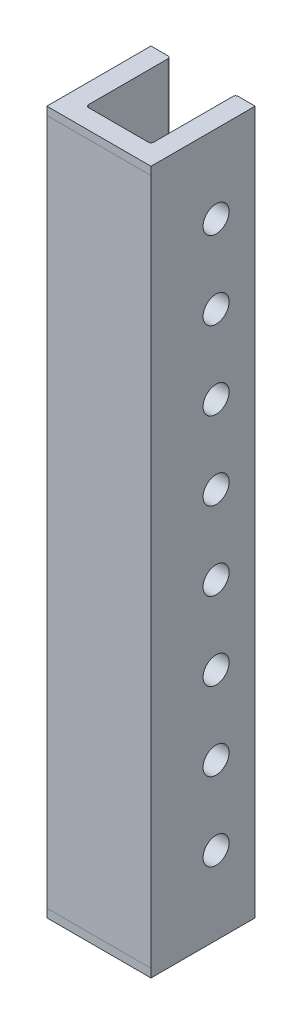
SolidWorks part; units mm, degrees
material "Plain Carbon Steel"
ref_plane "Front Plane" through (0, 0, 0) normal (0, 0, 1) x (1, 0, 0)
ref_plane "Top Plane" through (0, 0, 0) normal (0, 1, 0) x (1, 0, 0)
ref_plane "Right Plane" through (0, 0, 0) normal (1, 0, 0) x (0, 0, -1)
sketch "Sketch1" plane through (0, 0, 0) normal (0, 1, 0) x (1, 0, 0)
  line L0 (0, 0) -> (50.8, 0) construction
  line L1 (0, 0) -> (0, 9.525) construction
  line L2 (50.8, 0) -> (50.8, 9.525) construction
  line L3 (0, 9.525) -> (50.8, 9.525) construction
  line L4 (0, 0) -> (0, 50.8) construction
  line L5 (0, 50.8) -> (9.525, 50.8) construction
  line L6 (9.525, 50.8) -> (9.525, 9.525) construction
  line L7 (9.525, 9.525) -> (41.275, 9.525) construction
  line L8 (41.275, 9.525) -> (41.275, 50.8) construction
  line L9 (41.275, 50.8) -> (50.8, 50.8) construction
  line L10 (50.8, 50.8) -> (50.8, 9.525) construction
  line L11 (0, 0) -> (50.8, 0)
  line L12 (50.8, 0) -> (50.8, 50.8)
  line L13 (50.8, 50.8) -> (41.275, 50.8)
  line L14 (41.275, 50.8) -> (41.275, 9.525)
  line L15 (41.275, 9.525) -> (9.525, 9.525)
  line L16 (9.525, 9.525) -> (9.525, 50.8)
  line L17 (9.525, 50.8) -> (0, 50.8)
  line L18 (0, 50.8) -> (0, 0)
  dimension "D1" = 50.8
  dimension "D2" = 9.525
  dimension "D3" = 50.8
  dimension "D4" = 9.525
  dimension "D5" = 9.525
  dimension "D6" = 9.525
extrude "Boss-Extrude1" add sketch "Sketch1" along normal blind 342.9 contours L15 L16 L17 L18 L11 L12 L13 L14
sketch "Sketch2" plane through (50.8, 0, 0) normal (1, 0, 0) x (0, 0, -1)
  line L0 (31.75, 342.9) -> (31.75, 0) construction
  line L1 (0, 0) -> (50.8, 0) construction
  line L3 (31.75, 171.45) -> (0, 171.45) construction
  line L4 (0, 342.9) -> (0, 0) construction
  line L5 (0, 171.45) -> (50.8, 171.45) construction
  line L6 (50.8, 342.9) -> (50.8, 0) construction
  line L8 (0, 342.9) -> (50.8, 342.9) construction
  circle A0 centre (31.75, 304.8) radius 6.35
  circle A1 centre (31.75, 190.5) radius 6.35
  circle A2 centre (31.75, 228.6) radius 6.35
  circle A3 centre (31.75, 266.7) radius 6.35
  circle A4 centre (31.75, 76.2) radius 6.35
  circle A5 centre (31.75, 38.1) radius 6.35
  circle A7 centre (31.75, 152.4) radius 6.35
  circle A8 centre (31.75, 114.3) radius 6.35
  dimension "D1" = 38.1
  dimension "D2" = 171.45
  dimension "D5" = 12.7
  dimension "D6" = 12.7
  dimension "D7" = 12.7
  dimension "D8" = 152.4
  dimension "D11" = 12.7
  dimension "D12" = 12.7
  dimension "D13" = 12.7
  dimension "D15" = 12.7
  dimension "D16" = 12.7
  dimension "D3" = 76.2
  dimension "D4" = 114.3
  dimension "D9" = 19.05
  dimension "D10" = 190.5
  dimension "D14" = 228.6
  dimension "D17" = 38.1
  dimension "D18" = 38.1
  dimension "D19" = 38.1
extrude "Cut-Extrude1" cut sketch "Sketch2" against normal blind 304.8
fillet "Fillet1" radius 1.27 4 edges at (41.275, 171.45, -9.525) (9.525, 171.45, -50.8) (41.275, 171.45, -50.8) (9.525, 171.45, -9.525)
sketch "Sketch3" plane through (0, 0, 0) normal (0, 0, 1) x (1, 0, 0)
  line L0 (50.8, 342.9) -> (0, 342.9)
  line L1 (50.8, 342.9) -> (50.8, 338.9773)
  line L2 (0, 342.9) -> (0, 338.9773)
  line L3 (50.8, 338.9773) -> (0, 338.9773)
split line "Split Line1"
sketch "Sketch4" plane through (0, 0, 0) normal (0, 0, 1) x (1, 0, 0)
  line L0 (0, 0) -> (50.8, 0)
  line L1 (0, 0) -> (0, 4.0879)
  line L2 (50.8, 0) -> (50.8, 4.0879)
  line L3 (0, 4.0879) -> (50.8, 4.0879)
split line "Split Line3"
